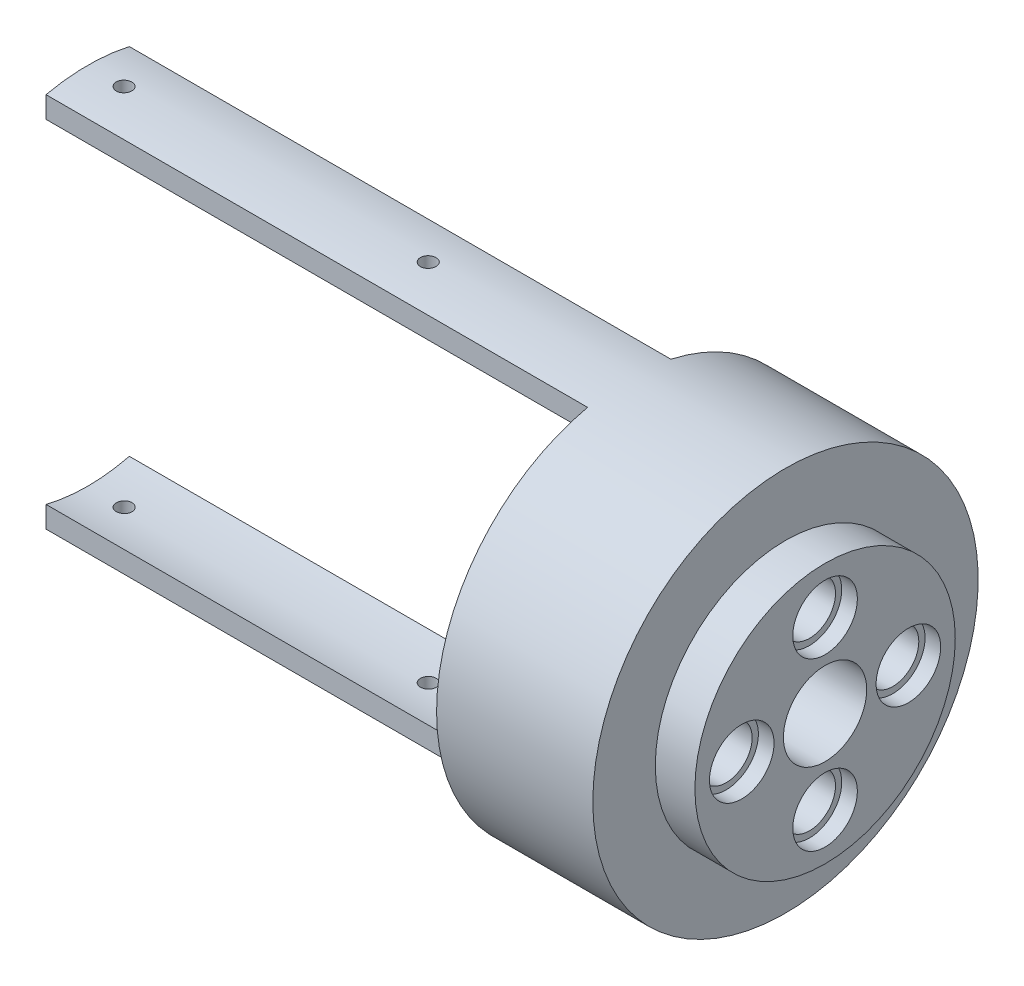
SolidWorks part; units mm, degrees
ref_plane "前视基准面" through (0, 0, 0) normal (0, 0, 1) x (1, 0, 0)
ref_plane "上视基准面" through (0, 0, 0) normal (0, 1, 0) x (1, 0, 0)
ref_plane "右视基准面" through (0, 0, 0) normal (1, 0, 0) x (0, 0, -1)
other "Configuration Table"
sketch "草图1" plane through (0, 0, 0) normal (1, 0, 0) x (0, 0, -1)
  circle A0 centre (0, 0) radius 4
  circle A1 centre (0, 8) radius 2.5
  circle A2 centre (0, 8) radius 3.1
  circle A3 centre (8, 0) radius 2.5
  circle A4 centre (8, 0) radius 3.1
  circle A5 centre (0, -8) radius 2.5
  circle A6 centre (0, -8) radius 3.1
  circle A7 centre (-8, 0) radius 2.5
  circle A8 centre (-8, 0) radius 3.1
  circle A9 centre (0, 0) radius 12.5
  point P18 (0, 0)
  dimension "D1" = 8
  dimension "D3" = 5
  dimension "D4" = 6.2
  dimension "D6" = 25
  dimension "D2" = 8
  dimension "D5" = 4
extrude "凸台-拉伸1" add sketch "草图1" along normal blind 7.8 contours A1 | A0 | A7 | A5 | A3 | A9 region at (0, 0, 0) region at (0, 8, 0) region at (0, 0, -8) region at (0, -8, 0) region at (0, 0, 8)
extrude "切除-拉伸1" cut sketch "草图1<3>" along normal blind 1.5 contours A2 A1 | A4 A3 | A6 A5 | A8 A7 region at (0, 8, 3.0123) region at (0, 0, -4.9877) region at (0, -8, 3.0123) region at (0, 0, 11.0123)
sketch "草图1<3>" plane through (0, 0, 0) normal (1, 0, 0) x (0, 0, -1) same geometry as "草图1"
extrude "切除-拉伸2" cut sketch "草图1<4>" against normal blind 1.5 from surface contours A2 A1 | A4 A3 | A6 A5 | A8 A7 region at (0, 8, 3.0123) region at (0, 0, -4.9877) region at (0, -8, 3.0123) region at (0, 0, 11.0123) starting at face at (7.8, -8, -2.5)
sketch "草图1<4>" plane through (0, 0, 0) normal (1, 0, 0) x (0, 0, -1) same geometry as "草图1"
sketch "草图2" plane through (0, 0, 0) normal (-1, 0, 0) x (0, 0, 1)
  line L7 (-4, -18.5) -> (4, -18.5)
  line L8 (-4, -18.5) -> (-4, 18.5)
  line L9 (-4, 18.5) -> (4, 18.5)
  line L10 (4, -18.5) -> (4, 18.5)
  line L11 (-4, -18.5) -> (4, 18.5) construction
  line L12 (-4, 18.5) -> (4, -18.5) construction
  circle A0 centre (0, 0) radius 16.5
  circle A1 centre (0, 0) radius 18.5
  circle A2 centre (0, 0) radius 12.5
  dimension "D1" = 33
  dimension "D3" = 25
  dimension "D5" = 37
  dimension "D4" = 8
extrude "凸台-拉伸2" add sketch "草图2" against normal blind 4 separate body contours A1 | A2
extrude "凸台-拉伸3" add sketch "草图2<3>" along normal blind 11 contours A1 | A0
sketch "草图2<3>" plane through (0, 0, 0) normal (-1, 0, 0) x (0, 0, 1) same geometry as "草图2"
extrude "凸台-拉伸4" add sketch "草图2<4>" along normal blind 52 from surface contours L8 A1 L10 A0 | L10 A1 L8 A0 region at (0, -17.3448, 0) region at (0, 17.3448, 0) starting at face at (-11, 0, 18.5)
sketch "草图2<4>" plane through (0, 0, 0) normal (-1, 0, 0) x (0, 0, 1) same geometry as "草图2"
sketch "草图5" plane through (0, 0, 0) normal (0, 1, 0) x (1, 0, 0)
  line L0 (-63, 4) -> (-63, -4) construction
  circle A0 centre (-59.5, 0) radius 0.75
  circle A1 centre (-30.3, 0) radius 0.75
  dimension "D2" = 1.5
  dimension "D1" = 3.5
  dimension "D3" = 29.2
extrude "切除-拉伸3" cut sketch "草图5" against normal through all both and the other way through all
